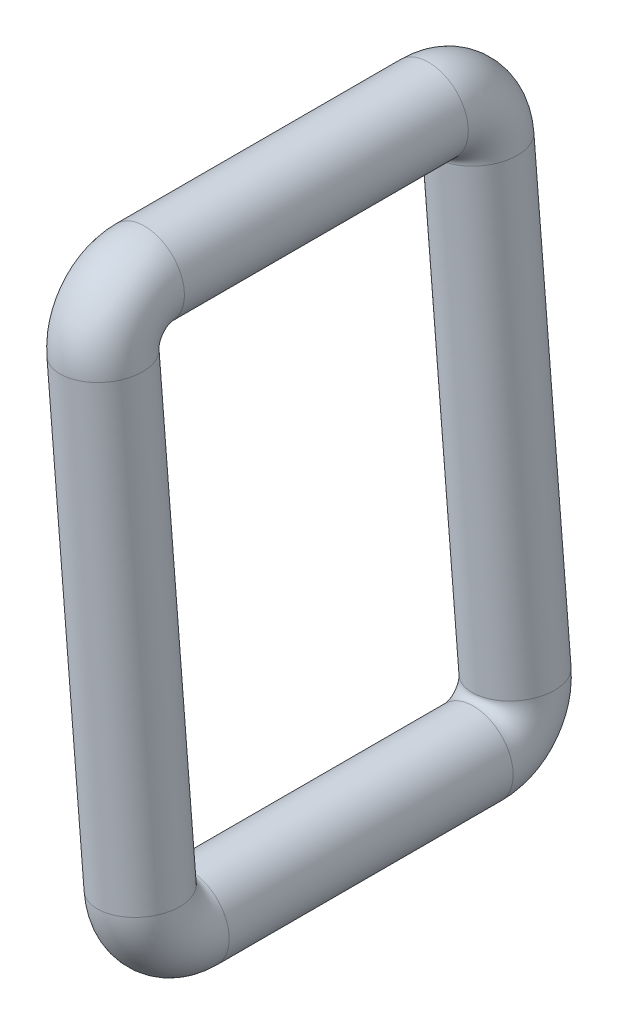
SolidWorks part; units mm, degrees
ref_plane "Front Plane" through (0, 0, 0) normal (0, 0, 1) x (1, 0, 0)
ref_plane "Top Plane" through (0, 0, 0) normal (0, 1, 0) x (1, 0, 0)
ref_plane "Right Plane" through (0, 0, 0) normal (1, 0, 0) x (0, 0, -1)
sketch "Sketch4" plane through (0, 0, 0) normal (0, 0, 1) x (1, 0, 0)
  arc A0 (11.1583, 0.9357) -> (11.3254, -0.8543) centre (10.8056, 0) ccw construction
  arc A1 (11.1583, 0.9357) -> (11.3254, -0.8543) centre (10.8056, 0) ccw
  arc A2 (11.949, -15.1308) -> (10.0934, -15.668) centre (11.0932, -15.648) ccw construction
  arc A3 (11.949, -15.1308) -> (10.0934, -15.668) centre (11.0932, -15.648) ccw
  point P6 (0, 0)
ref_axis "Axis1" through (10.8056, 0, 4.8) along (0, 0, -1)
ref_axis "Axis2" through (11.0932, -15.648, -3.4654) along (0, 0, -1)
ref_plane "Plane1" through (10.7304, 0.8983, 0) normal (0.9965, 0.0834, 0) x (0, 0, -1)
sketch "Sketch1" plane through (11.6611, -10.2194, 0) normal (-0.9965, -0.0834, 0) x (-0.0834, 0.9965, 0)
  line L0 (10.2552, -4.8) -> (10.2552, -2.3414) construction
  line L1 (1.5981, 0) -> (9.4552, 0)
  line L2 (0.7981, 0.8) -> (0.7981, 5.8)
  line L3 (1.5981, 6.6) -> (9.4552, 6.6)
  line L4 (10.2552, 0.8) -> (10.2552, 5.8)
  line L5 (0.7981, 3.4654) -> (0.7981, 4.4654) construction
  arc A0 (1.5981, 0) -> (0.7981, 0.8) centre (1.5981, 0.8) cw
  arc A1 (9.4552, 0) -> (10.2552, 0.8) centre (9.4552, 0.8) ccw
  arc A2 (9.4552, 6.6) -> (10.2552, 5.8) centre (9.4552, 5.8) cw
  arc A3 (0.7981, 5.8) -> (1.5981, 6.6) centre (1.5981, 5.8) cw
  point P7 (0.7981, 0)
  point P14 (11.1566, 6.6)
  dimension "D2" = 0.8
  dimension "D1" = 5
sweep "Sweep1" add path "Sketch1" circular profile diameter 1.4 parameters "D3"=1.4
